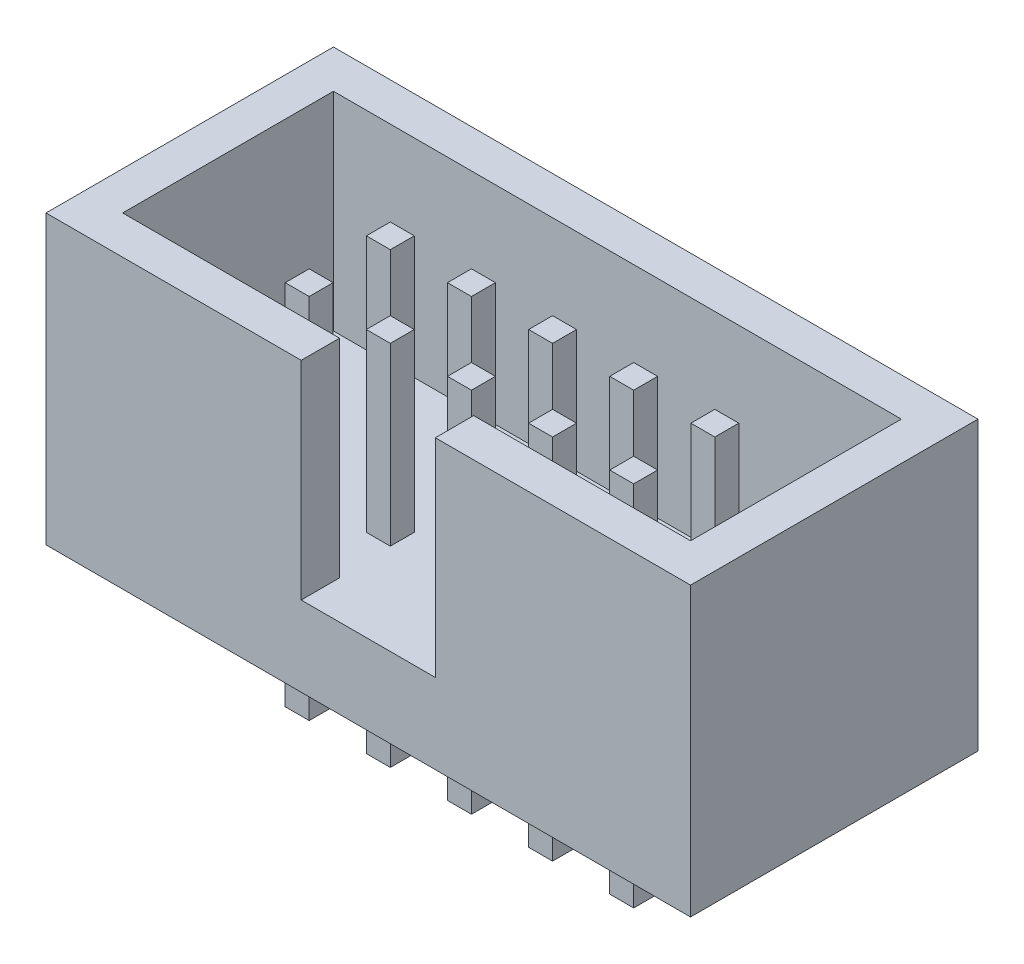
SolidWorks part; units mm, degrees
ref_plane "前视基准面" through (0, 0, 0) normal (0, 0, 1) x (1, 0, 0)
ref_plane "上视基准面" through (0, 0, 0) normal (0, 1, 0) x (1, 0, 0)
ref_plane "右视基准面" through (0, 0, 0) normal (1, 0, 0) x (0, 0, -1)
sketch "草图1" plane through (0, 0, 0) normal (0, 1, 0) x (1, 0, 0)
  line L0 (0, 85.0964) -> (0, -118.2031) construction
  line L1 (-10.09, 4.5) -> (10.09, 4.5)
  line L2 (-10.09, 4.5) -> (-10.09, -4.5)
  line L3 (-10.09, -4.5) -> (10.09, -4.5)
  line L4 (10.09, 4.5) -> (10.09, -4.5)
  line L5 (-200.5452, 0) -> (261.2352, 0) construction
  dimension "D1" = 9
  dimension "D2" = 20.18
extrude "拉伸1" add sketch "草图1" along normal blind 9
sketch "草图2" plane through (0, 9, 0) normal (0, 1, 0) x (-1, 0, 0)
  line L8 (-8.89, 3.3) -> (-8.89, -3.3)
  line L9 (8.89, 3.3) -> (-8.89, 3.3)
  line L10 (8.89, -3.3) -> (8.89, 3.3)
  line L11 (-8.89, -3.3) -> (8.89, -3.3)
  line L12 (-8.89, 3.3) -> (-8.89, -3.3)
  line L13 (8.89, 3.3) -> (-8.89, 3.3)
  line L14 (8.89, -3.3) -> (8.89, 3.3)
  line L15 (-8.89, -3.3) -> (8.89, -3.3)
  dimension "D1" = 1.2
extrude "切除-拉伸1" cut sketch "草图2" against normal blind 6.5
sketch "草图3" plane through (0, 0, 4.5) normal (0, 0, 1) x (1, 0, 0)
  line L0 (-10.09, 9) -> (10.09, 9) construction
  line L1 (-2.1, 9) -> (2.1, 9)
  line L2 (-2.1, 9) -> (-2.1, 2.5)
  line L3 (-2.1, 2.5) -> (2.1, 2.5)
  line L4 (2.1, 9) -> (2.1, 2.5)
  line L5 (-8.89, 2.5) -> (8.89, 2.5) construction
  line L6 (0, 9.4226) -> (0, -4.0288) construction
  dimension "D1" = 4.2
extrude "切除-拉伸2" cut sketch "草图3" against normal blind 6.5
sketch "草图5" plane through (0, 0, 0) normal (0, -1, 0) x (1, 0, 0)
  line L0 (0, 6.0683) -> (0, -6.9786) construction
  line L1 (-21.1981, 0) -> (21.4095, 0) construction
  line L2 (-2.4898, 1.27) -> (1.0953, 1.27) construction
  line L3 (-0.375, 0.895) -> (0.375, 0.895)
  line L4 (-0.375, 0.895) -> (-0.375, 1.645)
  line L5 (-0.375, 1.645) -> (0.375, 1.645)
  line L6 (0.375, 0.895) -> (0.375, 1.645)
  line L7 (2.165, 0.895) -> (2.915, 0.895)
  line L8 (2.165, 0.895) -> (2.165, 1.645)
  line L9 (2.165, 1.645) -> (2.915, 1.645)
  line L10 (2.915, 0.895) -> (2.915, 1.645)
  line L11 (4.705, 0.895) -> (5.455, 0.895)
  line L12 (4.705, 0.895) -> (4.705, 1.645)
  line L13 (4.705, 1.645) -> (5.455, 1.645)
  line L14 (5.455, 0.895) -> (5.455, 1.645)
  line L31 (-2.915, 0.895) -> (-2.165, 0.895)
  line L32 (-2.915, 0.895) -> (-2.915, 1.645)
  line L33 (-2.915, 1.645) -> (-2.165, 1.645)
  line L34 (-2.165, 0.895) -> (-2.165, 1.645)
  line L35 (-5.455, 0.895) -> (-4.705, 0.895)
  line L36 (-5.455, 0.895) -> (-5.455, 1.645)
  line L37 (-5.455, 1.645) -> (-4.705, 1.645)
  line L38 (-4.705, 0.895) -> (-4.705, 1.645)
  line L55 (-2.4898, -1.27) -> (1.0953, -1.27) construction
  line L72 (-4.705, -0.895) -> (-4.705, -1.645)
  line L73 (-5.455, -1.645) -> (-4.705, -1.645)
  line L74 (-5.455, -0.895) -> (-5.455, -1.645)
  line L75 (-5.455, -0.895) -> (-4.705, -0.895)
  line L76 (-2.165, -0.895) -> (-2.165, -1.645)
  line L77 (-2.915, -1.645) -> (-2.165, -1.645)
  line L78 (-2.915, -0.895) -> (-2.915, -1.645)
  line L79 (-2.915, -0.895) -> (-2.165, -0.895)
  line L96 (5.455, -0.895) -> (5.455, -1.645)
  line L97 (4.705, -1.645) -> (5.455, -1.645)
  line L98 (4.705, -0.895) -> (4.705, -1.645)
  line L99 (4.705, -0.895) -> (5.455, -0.895)
  line L100 (2.915, -0.895) -> (2.915, -1.645)
  line L101 (2.165, -1.645) -> (2.915, -1.645)
  line L102 (2.165, -0.895) -> (2.165, -1.645)
  line L103 (2.165, -0.895) -> (2.915, -0.895)
  line L104 (0.375, -0.895) -> (0.375, -1.645)
  line L105 (-0.375, -1.645) -> (0.375, -1.645)
  line L106 (-0.375, -0.895) -> (-0.375, -1.645)
  line L107 (-0.375, -0.895) -> (0.375, -0.895)
  line L108 (-7.995, 0.895) -> (-7.245, 0.895) [skipped]
  line L109 (-7.995, 0.895) -> (-7.995, 1.645) [skipped]
  line L110 (-7.995, 1.645) -> (-7.245, 1.645) [skipped]
  line L111 (-7.245, 0.895) -> (-7.245, 1.645) [skipped]
  line L112 (7.245, 0.895) -> (7.995, 0.895) [skipped]
  line L113 (7.245, 0.895) -> (7.245, 1.645) [skipped]
  line L114 (7.245, 1.645) -> (7.995, 1.645) [skipped]
  line L115 (7.995, 0.895) -> (7.995, 1.645) [skipped]
  dimension "D1" = 0.75
  dimension "D2" = 0.75
  dimension "D3" = 1.27
extrude "拉伸2" add sketch "草图5" along normal blind 3.5 and the other way offset from surface 1 other way up to face at (0, 9, 1.3)
